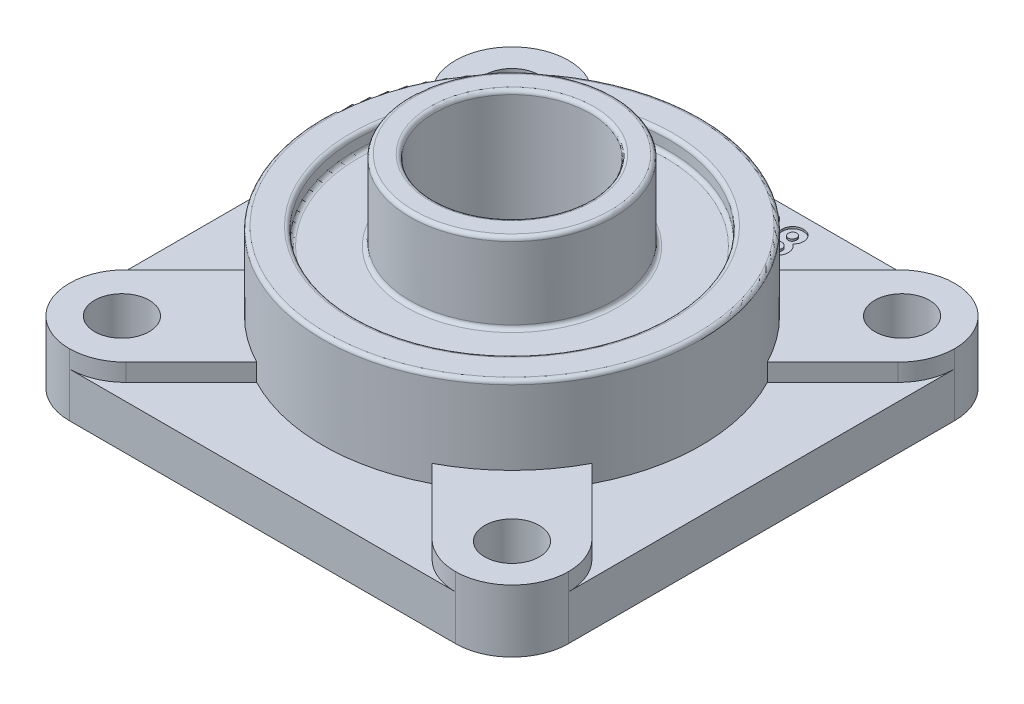
SolidWorks part; units mm, degrees
material "AISI 1020"
ref_plane "Plano frontal" through (0, 0, 0) normal (0, 0, 1) x (1, 0, 0)
ref_plane "Plano superior" through (0, 0, 0) normal (0, 1, 0) x (1, 0, 0)
ref_plane "Plano direito" through (0, 0, 0) normal (1, 0, 0) x (0, 0, -1)
sketch "Esboço1" plane through (0, 0, 0) normal (0, 1, 0) x (1, 0, 0)
  line L1 (-64, 64) -> (64, 64)
  line L2 (-64, 64) -> (-64, -64)
  line L3 (-64, -64) -> (64, -64)
  line L4 (64, 64) -> (64, -64)
  line L5 (-64, 64) -> (64, -64) construction
  line L6 (-64, -64) -> (64, 64) construction
  point P0 (0, 0)
  dimension "D1" = 128
  dimension "D2" = 128
extrude "Ressalto-extrusão1" add sketch "Esboço1" along normal blind 11.5
sketch "Esboço2" plane through (0, 11.5, 0) normal (0, 1, 0) x (1, 0, 0)
  line L0 (-64, 64) -> (64, -64)
  line L1 (64, -64) -> (-64, -64)
  line L2 (64, -64) -> (64, 64)
  line L3 (64, 64) -> (-64, 64)
  line L4 (-64, -64) -> (-64, 64)
  line L5 (64, -64) -> (-64, 64) construction
  line L6 (64, 64) -> (-64, -64) construction
  line L7 (-64, -64) -> (64, 64)
  line L8 (-43.4939, -64) -> (64, 43.4939)
  line L9 (-64, -43.4939) -> (43.4939, 64)
  line L10 (-64, 43.4939) -> (43.4939, -64)
  line L11 (-43.4939, 64) -> (64, -43.4939)
  line L12 (-53.747, 74.253) -> (74.253, -53.747) construction
  line L13 (-74.253, 53.747) -> (53.747, -74.253) construction
  line L14 (-74.253, -53.747) -> (53.747, 74.253) construction
  line L15 (-53.747, -74.253) -> (74.253, 53.747) construction
  point P0 (0, 0)
  line M1 (64, -64) -> (64, 64)
  line M2 (64, 64) -> (-64, 64)
  line M3 (-64, 64) -> (-64, -64)
  line M4 (-64, -64) -> (64, -64)
  dimension "D1" = 14.5
  dimension "D2" = 14.5
  dimension "D3" = 14.5
  dimension "D4" = 14.5
extrude "Ressalto-extrusão2" add sketch "Esboço2" along normal blind 4.5 contours L10 L9 L0 M3 | L11 L0 L9 M2 | L9 L11 L7 M2 | L7 L11 L8 L2 | L9 L10 L7 L0 | L11 L9 L0 L7 | L11 L7 L0 L8 | L7 L10 L8 L0 | L10 L9 L4 L7 | L10 L7 L8 M4 | L8 L10 L0 M4 | L11 L8 L0 M1
sketch "Esboço3" plane through (0, 0, 0) normal (0, -1, 0) x (1, 0, 0)
  circle A0 centre (0, 0) radius 48.5
  dimension "D1" = 97
extrude "Ressalto-extrusão3" add sketch "Esboço3" against normal blind 36
sketch "Esboço5" plane through (0, 0, 0) normal (0, -1, 0) x (1, 0, 0)
  circle A0 centre (0, 0) radius 26.15
  dimension "D1" = 52.3
extrude "Ressalto-extrusão4" add sketch "Esboço5" against normal blind 52
sketch "Esboço6" plane through (0, 36, 0) normal (0, 1, 0) x (1, 0, 0)
  circle A0 centre (0, 0) radius 40.25
  circle A1 centre (0, 0) radius 26.15
  dimension "D1" = 80.5
  dimension "D2" = 52.3
extrude "Corte-extrusão1" cut sketch "Esboço6" against normal blind 4.5
sketch "Esboço7" plane through (0, 52, 0) normal (0, 1, 0) x (1, 0, 0)
  circle A0 centre (0, 0) radius 20
  dimension "D1" = 40
extrude "Corte-extrusão2" cut sketch "Esboço7" against normal through all
sketch "Esboço8" plane through (0, 16, 0) normal (0, 1, 0) x (1, 0, 0)
  line L1 (50, -50) -> (-50, -50)
  line L2 (50, -50) -> (50, 50)
  line L3 (50, 50) -> (-50, 50)
  line L4 (-50, -50) -> (-50, 50)
  line L5 (50, -50) -> (-50, 50) construction
  line L6 (50, 50) -> (-50, -50) construction
  circle A0 centre (-50, 50) radius 7
  circle A1 centre (50, 50) radius 7
  circle A2 centre (50, -50) radius 7
  circle A3 centre (-50, -50) radius 7
  point P0 (0, 0)
  dimension "D2" = 14
  dimension "D1" = 100
extrude "Corte-extrusão3" cut sketch "Esboço8" against normal through all contours L4 A3 L1 | L1 A3 L4 | L3 A0 L4 | L4 A0 L3 | L2 A1 L3 | L3 A1 L2 | L2 A2 L1 | L1 A2 L2
fillet "Filete4" radius 14.5 24 edges at (-53.747, 16, -64) (-64, 16, -53.747) (-64, 16, 53.747) (-53.747, 16, 64) (53.747, 16, 64) (64, 16, 53.747) (64, 16, -53.747) (53.747, 16, -64) (64, 8, 64) (-64, 8, 64) (-64, 8, -64) (64, 8, -64)
fillet "Filete5" radius 1 4 edges at (0, 52, 20) (0, 52, -26.15) (0, 36, 40.25) (0, 36, -48.5)
sketch "Esboço9" plane through (0, 11.5, 0) normal (0, 1, 0) x (1, 0, 0)
  text T0 "<b>F 208</b>" font "Century Gothic" height in points 36
extrude "Corte-extrusão4" cut sketch "Esboço9" against normal blind 0.5
fillet "Filete6" radius 1 2 edges at (0, 31.5, 26.15) (0, 31.5, 40.25)
